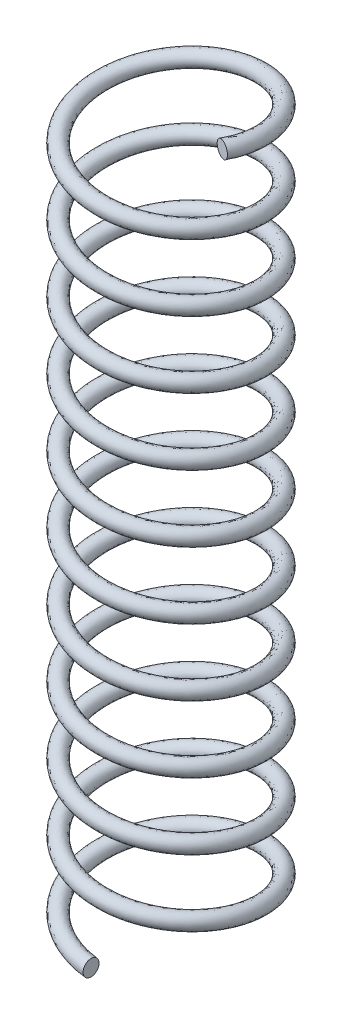
SolidWorks part; units mm, degrees
ref_plane "正面" through (0, 0, 0) normal (0, 0, 1) x (1, 0, 0)
ref_plane "平面" through (0, 0, 0) normal (0, 1, 0) x (1, 0, 0)
ref_plane "右側面" through (0, 0, 0) normal (1, 0, 0) x (0, 0, -1)
sketch "ｽｹｯﾁ2" plane through (0, 0, 0) normal (0, 1, 0) x (1, 0, 0)
  circle A0 centre (0, 0) radius 6
  dimension "D1" = 12
curve "ﾍﾘｶﾙ ｶｰﾌﾞ/ｽﾊﾟｲﾗﾙ ｶｰﾌﾞ1" pitch 5 height 54 turns 10.8
sketch "ｽｹｯﾁ3" plane through (0, 0, 0) normal (1, 0, 0) x (0, 0, -1)
  circle A0 centre (-6, 0) radius 0.6
  spline S0 degree 3 poles (1990.0977, 121.1741) (267.3312, -9.8483) (-25.6251, -4.3295) (-4.3382, 0.6278) (-2.3252, 0.9419) (0.045, 1.2558) (2.4083, 1.5698) (4.4016, 1.8837) (5.7186, 2.1977) (6.157, 2.5116) (5.6495, 2.8256) (4.2739, 3.1395) (2.2417, 3.4535) (-0.135, 3.7674) (-2.4908, 4.0814) (-4.464, 4.3953) (-5.7514, 4.7093) (-6.1551, 5.0233) (-5.6131, 5.3372) (-4.2087, 5.6512) (-2.1576, 5.9651) (0.2249, 6.2791) (2.5729, 6.593) (4.5255, 6.907) (5.7829, 7.2209) (6.1518, 7.5349) (5.5755, 7.8488) (4.1425, 8.1628) (2.0731, 8.4767) (-0.3148, 8.7907) (-2.6543, 9.1047) (-4.5861, 9.4186) (-5.8132, 9.7326) (-6.1472, 10.0465) (-5.5367, 10.3605) (-4.0755, 10.6744) (-1.9882, 10.9884) (0.4046, 11.3023) (2.7352, 11.6163) (4.6456, 11.9302) (5.8422, 12.2442) (6.1413, 12.5581) (5.4967, 12.8721) (4.0076, 13.186) (1.9028, 13.5) (-0.4943, 13.814) (-2.8156, 14.1279) (-4.7042, 14.4419) (-5.87, 14.7558) (-6.134, 15.0698) (-5.4556, 15.3837) (-3.9389, 15.6977) (-1.8171, 16.0116) (0.584, 16.3256) (2.8953, 16.6395) (4.7617, 16.9535) (5.8966, 17.2674) (6.1255, 17.5814) (5.4133, 17.8953) (3.8693, 18.2093) (1.7309, 18.5233) (-0.6735, 18.8372) (-2.9744, 19.1512) (-4.8183, 19.4651) (-5.9219, 19.7791) (-6.1157, 20.093) (-5.3698, 20.407) (-3.7989, 20.7209) (-1.6444, 21.0349) (0.7628, 21.3488) (3.0528, 21.6628) (4.8738, 21.9767) (5.9459, 22.2907) (6.1045, 22.6047) (5.3252, 22.9186) (3.7277, 23.2326) (1.5575, 23.5465) (-0.852, 23.8605) (-3.1306, 24.1744) (-4.9283, 24.4884) (-5.9687, 24.8023) (-6.0921, 25.1163) (-5.2794, 25.4302) (-3.6557, 25.7442) (-1.4703, 26.0581) (0.941, 26.3721) (3.2078, 26.686) (4.9817, 27) (5.9902, 27.314) (6.0783, 27.6279) (5.2326, 27.9419) (3.5829, 28.2558) (1.3827, 28.5698) (-1.0299, 28.8837) (-3.2842, 29.1977) (-5.034, 29.5116) (-6.0104, 29.8256) (-6.0633, 30.1395) (-5.1846, 30.4535) (-3.5093, 30.7674) (-1.2949, 31.0814) (1.1185, 31.3953) (3.36, 31.7093) (5.0853, 32.0233) (6.0293, 32.3372) (6.0469, 32.6512) (5.1355, 32.9651) (3.435, 33.2791) (1.2068, 33.593) (-1.2068, 33.907) (-3.435, 34.2209) (-5.1355, 34.5349) (-6.0469, 34.8488) (-6.0293, 35.1628) (-5.0853, 35.4767) (-3.36, 35.7907) (-1.1185, 36.1047) (1.2949, 36.4186) (3.5093, 36.7326) (5.1846, 37.0465) (6.0633, 37.3605) (6.0104, 37.6744) (5.034, 37.9884) (3.2842, 38.3023) (1.0299, 38.6163) (-1.3827, 38.9302) (-3.5829, 39.2442) (-5.2326, 39.5581) (-6.0783, 39.8721) (-5.9902, 40.186) (-4.9817, 40.5) (-3.2078, 40.814) (-0.941, 41.1279) (1.4703, 41.4419) (3.6557, 41.7558) (5.2794, 42.0698) (6.0921, 42.3837) (5.9687, 42.6977) (4.9283, 43.0116) (3.1306, 43.3256) (0.852, 43.6395) (-1.5575, 43.9535) (-3.7277, 44.2674) (-5.3252, 44.5814) (-6.1045, 44.8953) (-5.9459, 45.2093) (-4.8738, 45.5233) (-3.0528, 45.8372) (-0.7628, 46.1512) (1.6444, 46.4651) (3.7989, 46.7791) (5.3698, 47.093) (6.1157, 47.407) (5.9219, 47.7209) (4.8183, 48.0349) (2.9744, 48.3488) (0.6735, 48.6628) (-1.7309, 48.9767) (-3.8693, 49.2907) (-5.4133, 49.6047) (-6.1255, 49.9186) (-5.8966, 50.2326) (-4.7617, 50.5465) (-2.8953, 50.8605) (-0.584, 51.1744) (1.8171, 51.4884) (3.9389, 51.8023) (5.4556, 52.1163) (6.134, 52.4302) (5.87, 52.7442) (4.7043, 53.0581) (2.815, 53.3722) (-22.6074, 56.8104) (-62.3399, 60.4585) (1997.7753, 21.1757) knots -0.25831 -0.25831 -0.25831 -0.25831 0.005814 0.011628 0.017442 0.023256 0.02907 0.034884 0.040698 0.046512 0.052326 0.05814 0.063953 0.069767 0.075581 0.081395 0.087209 0.093023 0.098837 0.104651 0.110465 0.116279 0.122093 0.127907 0.133721 0.139535 0.145349 0.151163 0.156977 0.162791 0.168605 0.174419 0.180233 0.186047 0.19186 0.197674 0.203488 0.209302 0.215116 0.22093 0.226744 0.232558 0.238372 0.244186 0.25 0.255814 0.261628 0.267442 0.273256 0.27907 0.284884 0.290698 0.296512 0.302326 0.30814 0.313953 0.319767 0.325581 0.331395 0.337209 0.343023 0.348837 0.354651 0.360465 0.366279 0.372093 0.377907 0.383721 0.389535 0.395349 0.401163 0.406977 0.412791 0.418605 0.424419 0.430233 0.436047 0.44186 0.447674 0.453488 0.459302 0.465116 0.47093 0.476744 0.482558 0.488372 0.494186 0.5 0.505814 0.511628 0.517442 0.523256 0.52907 0.534884 0.540698 0.546512 0.552326 0.55814 0.563953 0.569767 0.575581 0.581395 0.587209 0.593023 0.598837 0.604651 0.610465 0.616279 0.622093 0.627907 0.633721 0.639535 0.645349 0.651163 0.656977 0.662791 0.668605 0.674419 0.680233 0.686047 0.69186 0.697674 0.703488 0.709302 0.715116 0.72093 0.726744 0.732558 0.738372 0.744186 0.75 0.755814 0.761628 0.767442 0.773256 0.77907 0.784884 0.790698 0.796512 0.802326 0.80814 0.813953 0.819767 0.825581 0.831395 0.837209 0.843023 0.848837 0.854651 0.860465 0.866279 0.872093 0.877907 0.883721 0.889535 0.895349 0.901163 0.906977 0.912791 0.918605 0.924419 0.930233 0.936047 0.94186 0.947674 0.953488 0.959302 0.965116 0.97093 0.976744 0.982558 0.988372 0.994186 1.173811 1.173811 1.173811 1.173811 only from (-6, 0) to (-1.8541, 54) construction
  spline S1 degree 3 poles (-6, 0) (-6, 0.104) (-5.6846, 0.3143) (-4.3382, 0.6278) (-2.3252, 0.9419) (0.045, 1.2558) (2.4083, 1.5698) (4.4016, 1.8837) (5.7186, 2.1977) (6.157, 2.5116) (5.6495, 2.8256) (4.2739, 3.1395) (2.2417, 3.4535) (-0.135, 3.7674) (-2.4908, 4.0814) (-4.464, 4.3953) (-5.7514, 4.7093) (-6.1551, 5.0233) (-5.6131, 5.3372) (-4.2087, 5.6512) (-2.1576, 5.9651) (0.2249, 6.2791) (2.5729, 6.593) (4.5255, 6.907) (5.7829, 7.2209) (6.1518, 7.5349) (5.5755, 7.8488) (4.1425, 8.1628) (2.0731, 8.4767) (-0.3148, 8.7907) (-2.6543, 9.1047) (-4.5861, 9.4186) (-5.8132, 9.7326) (-6.1472, 10.0465) (-5.5367, 10.3605) (-4.0755, 10.6744) (-1.9882, 10.9884) (0.4046, 11.3023) (2.7352, 11.6163) (4.6456, 11.9302) (5.8422, 12.2442) (6.1413, 12.5581) (5.4967, 12.8721) (4.0076, 13.186) (1.9028, 13.5) (-0.4943, 13.814) (-2.8156, 14.1279) (-4.7042, 14.4419) (-5.87, 14.7558) (-6.134, 15.0698) (-5.4556, 15.3837) (-3.9389, 15.6977) (-1.8171, 16.0116) (0.584, 16.3256) (2.8953, 16.6395) (4.7617, 16.9535) (5.8966, 17.2674) (6.1255, 17.5814) (5.4133, 17.8953) (3.8693, 18.2093) (1.7309, 18.5233) (-0.6735, 18.8372) (-2.9744, 19.1512) (-4.8183, 19.4651) (-5.9219, 19.7791) (-6.1157, 20.093) (-5.3698, 20.407) (-3.7989, 20.7209) (-1.6444, 21.0349) (0.7628, 21.3488) (3.0528, 21.6628) (4.8738, 21.9767) (5.9459, 22.2907) (6.1045, 22.6047) (5.3252, 22.9186) (3.7277, 23.2326) (1.5575, 23.5465) (-0.852, 23.8605) (-3.1306, 24.1744) (-4.9283, 24.4884) (-5.9687, 24.8023) (-6.0921, 25.1163) (-5.2794, 25.4302) (-3.6557, 25.7442) (-1.4703, 26.0581) (0.941, 26.3721) (3.2078, 26.686) (4.9817, 27) (5.9902, 27.314) (6.0783, 27.6279) (5.2326, 27.9419) (3.5829, 28.2558) (1.3827, 28.5698) (-1.0299, 28.8837) (-3.2842, 29.1977) (-5.034, 29.5116) (-6.0104, 29.8256) (-6.0633, 30.1395) (-5.1846, 30.4535) (-3.5093, 30.7674) (-1.2949, 31.0814) (1.1185, 31.3953) (3.36, 31.7093) (5.0853, 32.0233) (6.0293, 32.3372) (6.0469, 32.6512) (5.1355, 32.9651) (3.435, 33.2791) (1.2068, 33.593) (-1.2068, 33.907) (-3.435, 34.2209) (-5.1355, 34.5349) (-6.0469, 34.8488) (-6.0293, 35.1628) (-5.0853, 35.4767) (-3.36, 35.7907) (-1.1185, 36.1047) (1.2949, 36.4186) (3.5093, 36.7326) (5.1846, 37.0465) (6.0633, 37.3605) (6.0104, 37.6744) (5.034, 37.9884) (3.2842, 38.3023) (1.0299, 38.6163) (-1.3827, 38.9302) (-3.5829, 39.2442) (-5.2326, 39.5581) (-6.0783, 39.8721) (-5.9902, 40.186) (-4.9817, 40.5) (-3.2078, 40.814) (-0.941, 41.1279) (1.4703, 41.4419) (3.6557, 41.7558) (5.2794, 42.0698) (6.0921, 42.3837) (5.9687, 42.6977) (4.9283, 43.0116) (3.1306, 43.3256) (0.852, 43.6395) (-1.5575, 43.9535) (-3.7277, 44.2674) (-5.3252, 44.5814) (-6.1045, 44.8953) (-5.9459, 45.2093) (-4.8738, 45.5233) (-3.0528, 45.8372) (-0.7628, 46.1512) (1.6444, 46.4651) (3.7989, 46.7791) (5.3698, 47.093) (6.1157, 47.407) (5.9219, 47.7209) (4.8183, 48.0349) (2.9744, 48.3488) (0.6735, 48.6628) (-1.7309, 48.9767) (-3.8693, 49.2907) (-5.4133, 49.6047) (-6.1255, 49.9186) (-5.8966, 50.2326) (-4.7617, 50.5465) (-2.8953, 50.8605) (-0.584, 51.1744) (1.8171, 51.4884) (3.9389, 51.8023) (5.4556, 52.1163) (6.134, 52.4302) (5.87, 52.7442) (4.7043, 53.0581) (2.815, 53.3722) (0.4965, 53.6857) (-1.1084, 53.896) (-1.8541, 54) knots 0 0 0 0 0.005814 0.011628 0.017442 0.023256 0.02907 0.034884 0.040698 0.046512 0.052326 0.05814 0.063953 0.069767 0.075581 0.081395 0.087209 0.093023 0.098837 0.104651 0.110465 0.116279 0.122093 0.127907 0.133721 0.139535 0.145349 0.151163 0.156977 0.162791 0.168605 0.174419 0.180233 0.186047 0.19186 0.197674 0.203488 0.209302 0.215116 0.22093 0.226744 0.232558 0.238372 0.244186 0.25 0.255814 0.261628 0.267442 0.273256 0.27907 0.284884 0.290698 0.296512 0.302326 0.30814 0.313953 0.319767 0.325581 0.331395 0.337209 0.343023 0.348837 0.354651 0.360465 0.366279 0.372093 0.377907 0.383721 0.389535 0.395349 0.401163 0.406977 0.412791 0.418605 0.424419 0.430233 0.436047 0.44186 0.447674 0.453488 0.459302 0.465116 0.47093 0.476744 0.482558 0.488372 0.494186 0.5 0.505814 0.511628 0.517442 0.523256 0.52907 0.534884 0.540698 0.546512 0.552326 0.55814 0.563953 0.569767 0.575581 0.581395 0.587209 0.593023 0.598837 0.604651 0.610465 0.616279 0.622093 0.627907 0.633721 0.639535 0.645349 0.651163 0.656977 0.662791 0.668605 0.674419 0.680233 0.686047 0.69186 0.697674 0.703488 0.709302 0.715116 0.72093 0.726744 0.732558 0.738372 0.744186 0.75 0.755814 0.761628 0.767442 0.773256 0.77907 0.784884 0.790698 0.796512 0.802326 0.80814 0.813953 0.819767 0.825581 0.831395 0.837209 0.843023 0.848837 0.854651 0.860465 0.866279 0.872093 0.877907 0.883721 0.889535 0.895349 0.901163 0.906977 0.912791 0.918605 0.924419 0.930233 0.936047 0.94186 0.947674 0.953488 0.959302 0.965116 0.97093 0.976744 0.982558 0.988372 0.994186 1 1 1 1
  point P2 (0, 0)
  point P5 (0, 0)
  dimension "D1" = 1.2
sweep "ｽｲｰﾌﾟ1" add profiles "ｽｹｯﾁ3" path "ﾍﾘｶﾙ ｶｰﾌﾞ/ｽﾊﾟｲﾗﾙ ｶｰﾌﾞ1"
